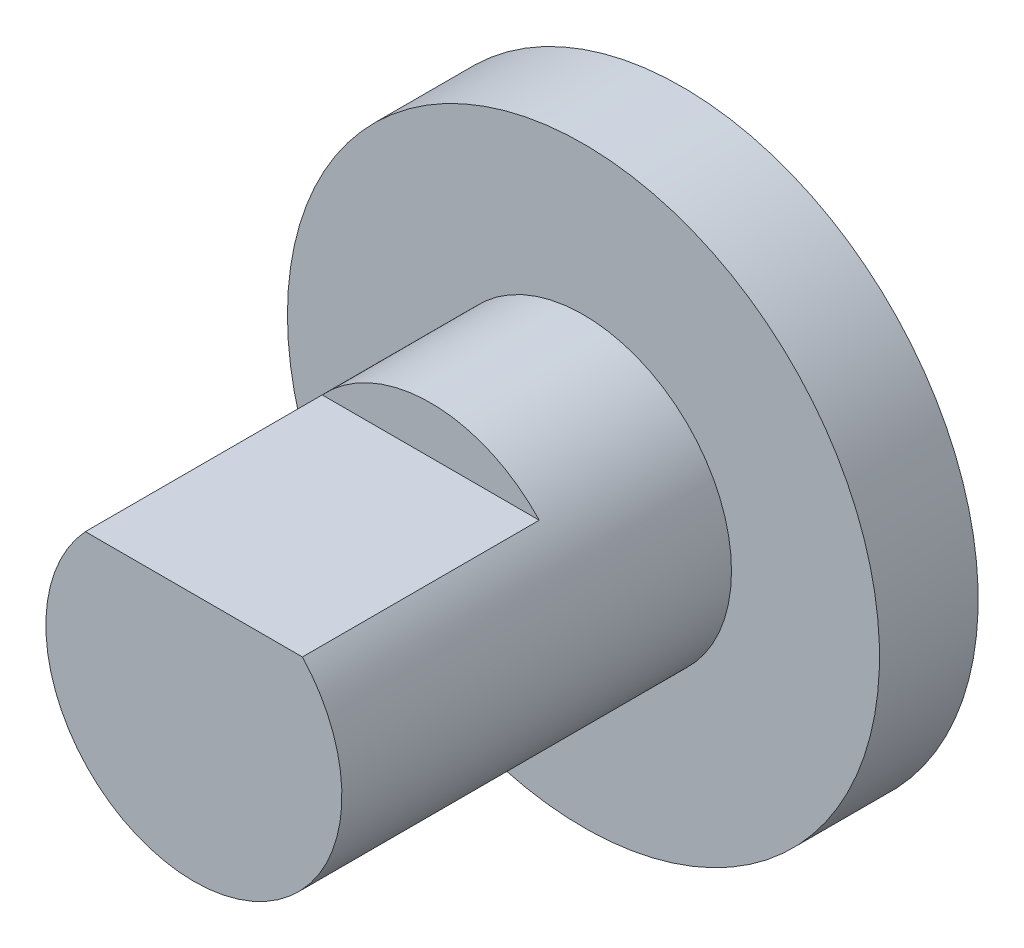
SolidWorks part; units mm, degrees
ref_plane "Front Plane" through (0, 0, 0) normal (0, 0, 1) x (1, 0, 0)
ref_plane "Top Plane" through (0, 0, 0) normal (0, 1, 0) x (1, 0, 0)
ref_plane "Right Plane" through (0, 0, 0) normal (1, 0, 0) x (0, 0, -1)
sketch "Sketch1" plane through (0, 0, 0) normal (0, 0, 1) x (1, 0, 0)
  circle A0 centre (0, 0) radius 7.5
  dimension "D1" = 15
extrude "Boss-Extrude1" add sketch "Sketch1" along normal blind 19.74
sketch "Sketch2" plane through (0, 0, 0) normal (0, 0, -1) x (-1, 0, 0)
  circle A0 centre (0, 0) radius 15
  dimension "D1" = 30
extrude "Boss-Extrude2" add sketch "Sketch2" along normal blind 5
sketch "Sketch3" plane through (0, 0, 19.74) normal (0, 0, 1) x (1, 0, 0)
  line L0 (5.5268, 5.07) -> (5.4991, 5.1)
  line L1 (5.4991, 5.1) -> (-5.4991, 5.1)
  arc A0 (5.5268, 5.07) -> (-5.4991, 5.1) centre (0, 0) ccw
  dimension "D2" = 15
  dimension "D1" = 5.1
extrude "Cut-Extrude1" cut sketch "Sketch3" against normal blind 12 contours L1 A0 region at (0, 6.0745, 19.74)
